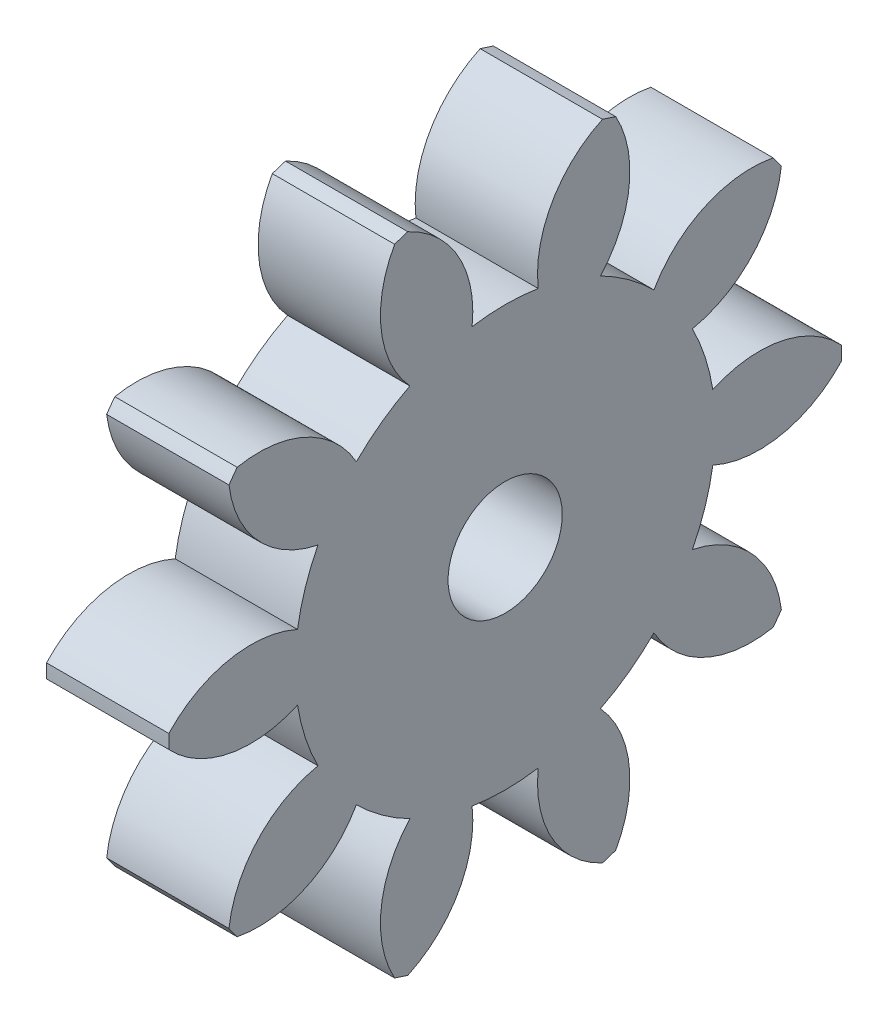
SolidWorks part; units mm, degrees
ref_plane "Plane1" through (0, 0, 0) normal (0, 0, 1) x (1, 0, 0)
ref_plane "Plane2" through (0, 0, 0) normal (0, 1, 0) x (1, 0, 0)
ref_plane "Plane3" through (0, 0, 0) normal (1, 0, 0) x (0, 0, -1)
sketch "HoldingSke" plane through (0, 0, 0) normal (0, 1, 0) x (1, 0, 0)
  line L0 (0, 0) -> (0.7162, -0.1263)
  line L1 (-15, 0) -> (100, 0) construction
  line L2 (0, 0) -> (-2.1039, 2.3779)
  line L3 (0, 0) -> (-11.863, 4.5341)
  line L4 (0, 0) -> (8.5048, 1.4996)
  line L5 (0, 0) -> (-46.8476, -17.4728)
  line L6 (0, 0) -> (-1.6579, -1.1186)
  line L7 (-2.1039, 2.3779) -> (8.6586, 51.2059)
  line L8 (-76.2, 54.61) -> (-75.3, 54.61)
  line L9 (-71.009, 38.7566) -> (-53.1078, 45.2721)
  line L10 (-76.2, 71.12) -> (104.1128, 71.12)
  line L11 (0, 0) -> (-2, 0)
  line L12 (-76.2, 101.6) -> (-76.151, 101.6)
  line L13 (24.9733, 27.94) -> (52.9518, 28.4284)
  line L14 (24.9733, 27.94) -> (24.9743, 27.94)
  line L15 (24.9733, 27.94) -> (100.4006, 29.5858)
  line L16 (-63.627, -1.375) -> (-12.827, -1.375)
  circle A0 centre (0, 0) radius 2.5
  circle A1 centre (0, 0) radius 5.1552
  circle A2 centre (0, 0) radius 37.5
  circle A3 centre (0, 0) radius 2.5
  dimension "MHD" = 10.3105
  dimension "Hub_dia" = 75
  dimension "Bore" = 5
  dimension "MBD" = 5
  dimension "Num_teeth" = 10
  dimension "Pitch" = 0.7273
  dimension "Overall_len" = 50
  dimension "Show_teeth" = 10
  dimension "Thickness" = 2
  dimension "OAL" = 50.0001
  dimension "T_dim" = 0.9
  dimension "Ap" = 20
  dimension "H" = 19.05
  dimension "Pitch_radius" = 180.3128
  dimension "Width" = 2
  dimension "Backlash" = 0.049
  dimension "Addendum_fac" = 1
  dimension "Dedendum_fac" = 1.25
  dimension "Clearance_fac" = 0.25
  dimension "Dedendum_add" = 0.001
  dimension "Module" = 1.375
sketch "BasProSke" plane through (0, 0, 0) normal (0, 1, 0) x (1, 0, 0)
  line L0 (-10, 0) -> (60, 0) construction
  line L1 (0, 0) -> (0, 8.25)
  line L2 (0, 0) -> (2, 0)
  line L3 (2, 0) -> (2, 8.25)
  line L4 (2, 8.25) -> (0, 8.25)
  dimension "Thickness" = 2
  dimension "Diameter" = 16.5
revolve "Base-Revolve" add sketch "BasProSke" angle 360 about L0
sketch "TooCutSke" plane through (0, 0, 0) normal (1, 0, 0) x (0, 0, -1)
  line L1 (0, 0) -> (0, 107) construction
  line L2 (0, 0) -> (-1.1611, 6.7762) construction
  line L3 (0, 0) -> (-4.2047, 12.9408) construction
  line L4 (-1.1611, 6.7762) -> (-2.1024, 6.4704) construction
  arc A0 (0.8108, 5.0911) -> (-0.8108, 5.0911) centre (0, 0) ccw
  arc A1 (2.4218, 7.9131) -> (-2.4218, 7.9131) centre (0, 0) ccw
  circle A2 centre (0, 0) radius 6.875 construction
  circle A3 centre (0, 0) radius 6.4604 construction
  arc A4 (-0.8108, 5.0911) -> (-2.4218, 7.9131) centre (-3.5431, 5.4021) ccw
  arc A5 (2.4218, 7.9131) -> (0.8108, 5.0911) centre (3.5431, 5.4021) ccw
  dimension "Root_dia" = 10.3105
  dimension "Overcut_dia" = 16.5508
  dimension "Pitch_dia" = 13.75
  dimension "Base_dia" = 12.9208
  dimension "Flank_rad" = 2.75
  dimension "Half_ang" = 18
  dimension "Half_CT" = 0.9897
extrude "ToothCut" cut sketch "TooCutSke" along normal through all
fillet "Breaks" [suppressed] radius 0.0275 tangent propagation no
fillet "RootFillets" [suppressed] radius 0.3447
pattern_circular "TeethCuts" count 10 every 36 about axis through (-10, 0, 0) along (1, 0, 0) of "ToothCut", "RootFillets", "Breaks"
sketch "HubNeaOneSke" plane through (0, 0, 0) normal (-1, 0, 0) x (0, 0, 1)
  circle A0 centre (0, 0) radius 5.1552
  dimension "Diameter" = 10.3105
extrude "HubNearOne" [suppressed] add sketch "HubNeaOneSke" along normal blind 48.0001
sketch "HubNeaBotSke" plane through (0, 0, 0) normal (-1, 0, 0) x (0, 0, 1)
  circle A0 centre (0, 0) radius 5.1552
  dimension "Diameter" = 10.3105
extrude "HubNearBoth" [suppressed] add sketch "HubNeaBotSke" along normal blind 24
ref_plane "FarPln" through (2, 0, 0) normal (1, 0, 0) x (0, 0, -1)
sketch "HubFarSke" plane through (2, 0, 0) normal (1, 0, 0) x (0, 0, -1)
  circle A0 centre (0, 0) radius 5.1552
  dimension "Diameter" = 10.3105
extrude "HubFar" [suppressed] add sketch "HubFarSke" along normal blind 24
sketch "BorSke" plane through (0, 0, 0) normal (1, 0, 0) x (0, 0, -1)
  circle A0 centre (0, 0) radius 2.5
  dimension "Diameter" = 5
extrude "Bore" cut sketch "BorSke" along normal mid plane 100.0001
sketch "KeySke" plane through (0, 0, 0) normal (1, 0, 0) x (0, 0, -1)
  line L0 (-1, 0) -> (-1, 3.4)
  line L1 (-1, 3.4) -> (1, 3.4)
  line L2 (1, 3.4) -> (1, 0)
  line L3 (0, 0) -> (0, 34) construction
  line L4 (-1, 0) -> (1, 0)
  dimension "Width" = 2
  dimension "Offset" = 3.4
extrude "Keyway" [suppressed] cut sketch "KeySke" along normal mid plane 100.0001
pattern_circular "Keyway2" [suppressed] count 2 every 90 about axis through (-10, 0, 0) along (1, 0, 0)
sketch "Sketch1" plane through (2, 0, 0) normal (1, 0, 0) x (0, 0, -1)
  circle A0 centre (0, 0) radius 2.5
  circle A1 centre (0, 0) radius 1.4
  dimension "D1" = 5
  dimension "D2" = 2.8
extrude "Boss-Extrude1" add sketch "Sketch1" against normal up to surface (2 mm away) up to face at (0, 0, -2.5)
sketch "Sketch2" plane through (0, 0, 0) normal (-1, 0, 0) x (0, 0, 1)
  circle A0 centre (0, 0) radius 1.6
  circle A1 centre (0, 0) radius 2.8
extrude "Boss-Extrude2" add sketch "Sketch2" along normal up to surface (1 mm away)
chamfer "Chamfer1" distance 1.5 angle 45 1 edges at (0, 0, -2.8)
sketch "Sketch3" plane through (2, 0, 0) normal (1, 0, 0) x (0, 0, -1)
  circle A0 centre (0, 0) radius 1.5
  arc A40 (8.2482, 0.1704) -> (5.0925, 0.8021) centre (6.2326, -1.7004) ccw
  arc A41 (5.0925, 0.8021) -> (4.5914, 2.3443) centre (0, 0) ccw
  arc A42 (4.5914, 2.3443) -> (6.7731, 4.7104) centre (4.0428, 5.0391) ccw
  arc A43 (6.7731, 4.7104) -> (6.5728, 4.986) centre (0, 0) ccw
  arc A44 (6.5728, 4.986) -> (3.6484, 3.6422) centre (6.0417, 2.2878) ccw
  arc A45 (3.6484, 3.6422) -> (2.3365, 4.5953) centre (0, 0) ccw
  arc A46 (2.3365, 4.5953) -> (2.7109, 7.7919) centre (0.3088, 6.453) ccw
  arc A47 (2.7109, 7.7919) -> (2.3868, 7.8972) centre (0, 0) ccw
  arc A48 (2.3868, 7.8972) -> (0.8108, 5.0911) centre (3.5431, 5.4021) ccw
  arc A49 (0.8108, 5.0911) -> (-0.8108, 5.0911) centre (0, 0) ccw
  arc A50 (-0.8108, 5.0911) -> (-2.3868, 7.8972) centre (-3.5431, 5.4021) ccw
  arc A51 (-2.3868, 7.8972) -> (-2.7109, 7.7919) centre (0, 0) ccw
  arc A52 (-2.7109, 7.7919) -> (-2.3365, 4.5953) centre (-0.3088, 6.453) ccw
  arc A53 (-2.3365, 4.5953) -> (-3.6484, 3.6422) centre (0, 0) ccw
  arc A54 (-3.6484, 3.6422) -> (-6.5728, 4.986) centre (-6.0417, 2.2878) ccw
  arc A55 (-6.5728, 4.986) -> (-6.7731, 4.7104) centre (0, 0) ccw
  arc A56 (-6.7731, 4.7104) -> (-4.5914, 2.3443) centre (-4.0428, 5.0391) ccw
  arc A57 (-4.5914, 2.3443) -> (-5.0925, 0.8021) centre (0, 0) ccw
  arc A58 (-5.0925, 0.8021) -> (-8.2482, 0.1704) centre (-6.2326, -1.7004) ccw
  arc A59 (-8.2482, 0.1704) -> (-8.2482, -0.1704) centre (0, 0) ccw
  arc A60 (-8.2482, -0.1704) -> (-5.0925, -0.8021) centre (-6.2326, 1.7004) ccw
  arc A61 (-5.0925, -0.8021) -> (-4.5914, -2.3443) centre (0, 0) ccw
  arc A62 (-4.5914, -2.3443) -> (-6.7731, -4.7104) centre (-4.0428, -5.0391) ccw
  arc A63 (-6.7731, -4.7104) -> (-6.5728, -4.986) centre (0, 0) ccw
  arc A64 (-6.5728, -4.986) -> (-3.6484, -3.6422) centre (-6.0417, -2.2878) ccw
  arc A65 (-3.6484, -3.6422) -> (-2.3365, -4.5953) centre (0, 0) ccw
  arc A66 (-2.3365, -4.5953) -> (-2.7109, -7.7919) centre (-0.3088, -6.453) ccw
  arc A67 (-2.7109, -7.7919) -> (-2.3868, -7.8972) centre (0, 0) ccw
  arc A68 (-2.3868, -7.8972) -> (-0.8108, -5.0911) centre (-3.5431, -5.4021) ccw
  arc A69 (-0.8108, -5.0911) -> (0.8108, -5.0911) centre (0, 0) ccw
  arc A70 (0.8108, -5.0911) -> (2.3868, -7.8972) centre (3.5431, -5.4021) ccw
  arc A71 (2.3868, -7.8972) -> (2.7109, -7.7919) centre (0, 0) ccw
  arc A72 (2.7109, -7.7919) -> (2.3365, -4.5953) centre (0.3088, -6.453) ccw
  arc A73 (2.3365, -4.5953) -> (3.6484, -3.6422) centre (0, 0) ccw
  arc A74 (3.6484, -3.6422) -> (6.5728, -4.986) centre (6.0417, -2.2878) ccw
  arc A75 (6.5728, -4.986) -> (6.7731, -4.7104) centre (0, 0) ccw
  arc A76 (6.7731, -4.7104) -> (4.5914, -2.3443) centre (4.0428, -5.0391) ccw
  arc A77 (4.5914, -2.3443) -> (5.0925, -0.8021) centre (0, 0) ccw
  arc A78 (5.0925, -0.8021) -> (8.2482, -0.1704) centre (6.2326, 1.7004) ccw
  arc A79 (8.2482, -0.1704) -> (8.2482, 0.1704) centre (0, 0) ccw
  arc A80 (8.2482, 0.1704) -> (5.0925, 0.8021) centre (6.2326, -1.7004) ccw
  arc A81 (5.0925, 0.8021) -> (4.5914, 2.3443) centre (0, 0) ccw
  arc A82 (4.5914, 2.3443) -> (6.7731, 4.7104) centre (4.0428, 5.0391) ccw
  arc A83 (6.7731, 4.7104) -> (6.5728, 4.986) centre (0, 0) ccw
  arc A84 (6.5728, 4.986) -> (3.6484, 3.6422) centre (6.0417, 2.2878) ccw
  arc A85 (3.6484, 3.6422) -> (2.3365, 4.5953) centre (0, 0) ccw
  arc A86 (2.3365, 4.5953) -> (2.7109, 7.7919) centre (0.3088, 6.453) ccw
  arc A87 (2.7109, 7.7919) -> (2.3868, 7.8972) centre (0, 0) ccw
  arc A88 (2.3868, 7.8972) -> (0.8108, 5.0911) centre (3.5431, 5.4021) ccw
  arc A89 (0.8108, 5.0911) -> (-0.8108, 5.0911) centre (0, 0) ccw
  arc A90 (-0.8108, 5.0911) -> (-2.3868, 7.8972) centre (-3.5431, 5.4021) ccw
  arc A91 (-2.3868, 7.8972) -> (-2.7109, 7.7919) centre (0, 0) ccw
  arc A92 (-2.7109, 7.7919) -> (-2.3365, 4.5953) centre (-0.3088, 6.453) ccw
  arc A93 (-2.3365, 4.5953) -> (-3.6484, 3.6422) centre (0, 0) ccw
  arc A94 (-3.6484, 3.6422) -> (-6.5728, 4.986) centre (-6.0417, 2.2878) ccw
  arc A95 (-6.5728, 4.986) -> (-6.7731, 4.7104) centre (0, 0) ccw
  arc A96 (-6.7731, 4.7104) -> (-4.5914, 2.3443) centre (-4.0428, 5.0391) ccw
  arc A97 (-4.5914, 2.3443) -> (-5.0925, 0.8021) centre (0, 0) ccw
  arc A98 (-5.0925, 0.8021) -> (-8.2482, 0.1704) centre (-6.2326, -1.7004) ccw
  arc A99 (-8.2482, 0.1704) -> (-8.2482, -0.1704) centre (0, 0) ccw
  arc A100 (-8.2482, -0.1704) -> (-5.0925, -0.8021) centre (-6.2326, 1.7004) ccw
  arc A101 (-5.0925, -0.8021) -> (-4.5914, -2.3443) centre (0, 0) ccw
  arc A102 (-4.5914, -2.3443) -> (-6.7731, -4.7104) centre (-4.0428, -5.0391) ccw
  arc A103 (-6.7731, -4.7104) -> (-6.5728, -4.986) centre (0, 0) ccw
  arc A104 (-6.5728, -4.986) -> (-3.6484, -3.6422) centre (-6.0417, -2.2878) ccw
  arc A105 (-3.6484, -3.6422) -> (-2.3365, -4.5953) centre (0, 0) ccw
  arc A106 (-2.3365, -4.5953) -> (-2.7109, -7.7919) centre (-0.3088, -6.453) ccw
  arc A107 (-2.7109, -7.7919) -> (-2.3868, -7.8972) centre (0, 0) ccw
  arc A108 (-2.3868, -7.8972) -> (-0.8108, -5.0911) centre (-3.5431, -5.4021) ccw
  arc A109 (-0.8108, -5.0911) -> (0.8108, -5.0911) centre (0, 0) ccw
  arc A110 (0.8108, -5.0911) -> (2.3868, -7.8972) centre (3.5431, -5.4021) ccw
  arc A111 (2.3868, -7.8972) -> (2.7109, -7.7919) centre (0, 0) ccw
  arc A112 (2.7109, -7.7919) -> (2.3365, -4.5953) centre (0.3088, -6.453) ccw
  arc A113 (2.3365, -4.5953) -> (3.6484, -3.6422) centre (0, 0) ccw
  arc A114 (3.6484, -3.6422) -> (6.5728, -4.986) centre (6.0417, -2.2878) ccw
  arc A115 (6.5728, -4.986) -> (6.7731, -4.7104) centre (0, 0) ccw
  arc A116 (6.7731, -4.7104) -> (4.5914, -2.3443) centre (4.0428, -5.0391) ccw
  arc A117 (4.5914, -2.3443) -> (5.0925, -0.8021) centre (0, 0) ccw
  arc A118 (5.0925, -0.8021) -> (8.2482, -0.1704) centre (6.2326, 1.7004) ccw
  arc A119 (8.2482, -0.1704) -> (8.2482, 0.1704) centre (0, 0) ccw
  dimension "D1" = 0
extrude "Boss-Extrude3" add sketch "Sketch3" along normal blind 1
sketch "Sketch4" plane through (0, 0, 0) normal (-1, 0, 0) x (0, 0, 1)
  circle A0 centre (0, 0) radius 1.4 construction
  circle A1 centre (0, 0) radius 1.6
  circle A2 centre (0, 0) radius 1.6
  circle A3 centre (0, 0) radius 1.4
  dimension "D1" = 0
extrude "Boss-Extrude4" add sketch "Sketch4" along normal up to surface (1 mm away) up to face at (-1, 0, 3.3)
sketch "Sketch5" plane through (2, 0, 0) normal (1, 0, 0) x (0, 0, -1)
  circle A0 centre (0, 0) radius 1.4
  circle A1 centre (0, 0) radius 1.5
  circle A2 centre (0, 0) radius 1.5
  dimension "D1" = 0
extrude "Boss-Extrude5" add sketch "Sketch5" along normal up to surface (1 mm away) up to face at (3, 0, 0)
equation "' \"Module@HoldingSke\" = 6.35"
equation "' \"Num_teeth@HoldingSke\" = 12"
equation "' \"Ap@HoldingSke\" =  20"
equation "' \"Ap@HoldingSke\" = 20"
equation "' \"Width@HoldingSke\" = 0.5 * 25.4"
equation "' \"Hub_dia@HoldingSke\"= 1 * 25.4"
equation "' \"Hub_dia@HoldingSke\" = 1 * 25.4"
equation "' \"Overall_len@HoldingSke\" = 1.0 * 25.4"
equation "' \"Bore@HoldingSke\" = 0.75 * 25.4"
equation "' \"T_dim@HoldingSke\" = 0.1 * 25.4"
equation "' \"Width@KeySke\" = 0.25 * 25.4"
equation "' \"Show_teeth@HoldingSke\" = 13"
equation "' \"Backlash@HoldingSke\" = 0.009 * 25.4"
equation "' \"Addendum_fac@HoldingSke\" = 1.0"
equation "' \"Dedendum_fac@HoldingSke\" = 1.25"
equation "' \"Dedendum_add@HoldingSke\" = 0.00005 * 25.4"
equation "' \"Clearance_fac@HoldingSke\" = 0.25"
equation "\"Pitch@HoldingSke\" = 1 / \"Module@HoldingSke\""
equation "\"Overcut_dia@TooCutSke\" = (\"Num_teeth@HoldingSke\" + 2 * \"Addendum_fac@HoldingSke\") / \"Pitch@HoldingSke\" + 0.002 * 25.4"
equation "\"Pitch_dia@TooCutSke\" = \"Num_teeth@HoldingSke\" / \"Pitch@HoldingSke\""
equation "\"Base_dia@TooCutSke\" = \"Num_teeth@HoldingSke\" / \"Pitch@HoldingSke\" * cos((\"Ap@HoldingSke\"  * 3.14159265 / 180))"
equation "\"Root_dia@TooCutSke\" = (\"Num_teeth@HoldingSke\" + 2) / \"Pitch@HoldingSke\" - 2 * (\"Addendum_fac@HoldingSke\" + \"Dedendum_fac@HoldingSke\") / \"Pitch@HoldingSke\" - \"Dedendum_add@HoldingSke\" * 2"
equation "\"Half_ang@TooCutSke\" = 180 / \"Num_teeth@HoldingSke\""
equation "\"Half_CT@TooCutSke\" = \"Num_teeth@HoldingSke\" / \"Pitch@HoldingSke\" * sin((3.14159265 / 2 / \"Num_teeth@HoldingSke\")) / 2 - 7 * \"Backlash@HoldingSke\" / 4"
equation "\"Flank_rad@TooCutSke\" = \"Num_teeth@HoldingSke\" / \"Pitch@HoldingSke\" / 5"
equation "\"Radius@RootFillets\" = \"Clearance_fac@HoldingSke\" / \"Pitch@HoldingSke\" + \"Dedendum_add@HoldingSke\""
equation "\"Break_rad@Breaks\" = 0.02 / \"Pitch@HoldingSke\""
equation "\"Thickness@HoldingSke\" = \"Width@HoldingSke\""
equation "\"OAL@HoldingSke\" = \"Thickness@HoldingSke\""
equation "\"MHD@HoldingSke\" = (\"Num_teeth@HoldingSke\" + 2) / \"Pitch@HoldingSke\" - 2 * (\"Addendum_fac@HoldingSke\" + \"Dedendum_fac@HoldingSke\")  / \"Pitch@HoldingSke\" - \"Dedendum_add@HoldingSke\" * 2"
equation "\"MBD@HoldingSke\" = (\"Num_teeth@HoldingSke\" + 2) / \"Pitch@HoldingSke\" - 2 * (\"Addendum_fac@HoldingSke\" + \"Dedendum_fac@HoldingSke\")  / \"Pitch@HoldingSke\" - \"Dedendum_add@HoldingSke\" * 2 - 0.002 * 25.4"
equation "\"MHD@HoldingSke\" = ((sgn( \"MHD@HoldingSke\" - \"Hub_dia@HoldingSke\" )-1)*( \"MHD@HoldingSke\" - \"Hub_dia@HoldingSke\" ))/-2+ \"Hub_dia@HoldingSke\""
equation "\"MBD@HoldingSke\" = ((sgn( \"MBD@HoldingSke\" - \"Bore@HoldingSke\" )-1)*( \"MBD@HoldingSke\" - \"Bore@HoldingSke\" ))/-2+ \"Bore@HoldingSke\""
equation "\"OAL@HoldingSke\" = ((sgn( \"OAL@HoldingSke\" - \"Overall_len@HoldingSke\" )+1)*( \"OAL@HoldingSke\" - \"Overall_len@HoldingSke\" ))/2 + \"Overall_len@HoldingSke\" + 0.000002 * 25.4"
equation "\"Num_teeth@TeethCuts\" = int( \"Show_teeth@HoldingSke\" ) + 1"
equation "\"Num_teeth@TeethCuts\" = ((sgn( \"Num_teeth@TeethCuts\" - \"Num_teeth@HoldingSke\" )-1)*( \"Num_teeth@TeethCuts\" - \"Num_teeth@HoldingSke\" ))/-2+ \"Num_teeth@HoldingSke\""
equation "\"Num_teeth@TeethCuts\" = ((sgn( \"Num_teeth@TeethCuts\" - 2.0)+1)*( \"Num_teeth@TeethCuts\" - 2.0))/2 +2.0"
equation "\"Angle@TeethCuts\" = 360.0 / \"Num_teeth@HoldingSke\""
equation "\"Diameter@BasProSke\" = (\"Num_teeth@HoldingSke\" + 2 * \"Addendum_fac@HoldingSke\") / \"Pitch@HoldingSke\""
equation "\"Thickness@BasProSke\"  = \"Thickness@HoldingSke\""
equation "' \"Fillet_rad@BasProSke\" =  \"Thickness@HoldingSke\" * 0.05"
equation "' \"Fillet_rad@BasProSke\" = \"Thickness@HoldingSke\" * 0.05"
equation "\"MHD@HoldingSke\" = ((sgn( \"MHD@HoldingSke\" - \"Root_dia@TooCutSke\" )-1)*( \"MHD@HoldingSke\" - \"Root_dia@TooCutSke\" ))/-2+ \"Root_dia@TooCutSke\""
equation "\"Diameter@HubNeaOneSke\" = \"MHD@HoldingSke\""
equation "\"Length@HubNearOne\" = \"OAL@HoldingSke\" - \"Thickness@BasProSke\""
equation "\"Diameter@HubNeaBotSke\" = \"MHD@HoldingSke\""
equation "\"Length@HubNearBoth\" = ( \"OAL@HoldingSke\" - \"Thickness@BasProSke\" ) / 2.0"
equation "\"Thickness@FarPln\" = \"Thickness@BasProSke\""
equation "\"Diameter@HubFarSke\" = \"MHD@HoldingSke\""
equation "\"Length@HubFar\" = ( \"OAL@HoldingSke\" - \"Thickness@BasProSke\" ) / 2.0"
equation "\"Diameter@BorSke\" = \"MBD@HoldingSke\""
equation "\"D1@Bore\" = \"OAL@HoldingSke\" * 2.0"
equation "\"D1@Keyway\" = \"OAL@HoldingSke\" * 2.0"
equation "\"Offset@KeySke\" = \"T_dim@HoldingSke\" + \"MBD@HoldingSke\" / 2.0"
